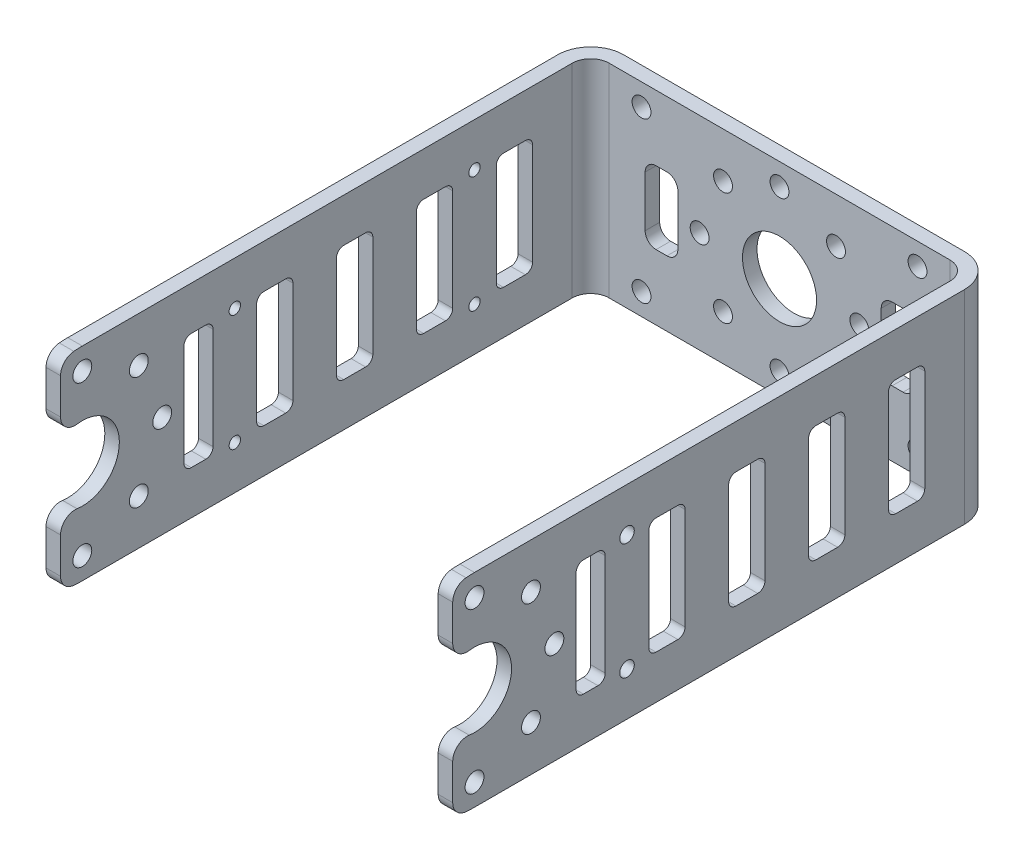
SolidWorks part; units mm, degrees
material "1060 Alloy"
ref_plane "Front Plane" through (0, 0, 0) normal (0, 0, 1) x (1, 0, 0)
ref_plane "Top Plane" through (0, 0, 0) normal (0, 1, 0) x (1, 0, 0)
ref_plane "Right Plane" through (0, 0, 0) normal (1, 0, 0) x (0, 0, -1)
ref_plane "Plane1" through (-2, 0, 0) normal (-1, 0, 0) x (0, -1, 0)
sketch "Sketch1" plane through (-2, 0, 0) normal (-1, 0, 0) x (0, -1, 0)
  line L0 (-28, 72) -> (0, 72)
  line L1 (-0.3252, 75) -> (-27.6748, 75)
  arc A0 (-27.6748, 75) -> (-28, 72) centre (-14, 72) ccw
  arc A1 (0, 72) -> (-0.3252, 75) centre (-14, 72) ccw
extrude "Boss-Extrude1" add sketch "Sketch1" against normal blind 54
sketch "Sketch2" plane through (0, 0, 72) normal (0, 0, -1) x (-1, 0, 0)
  line L0 (-52, 28) -> (2, 28)
  line L1 (2, 28) -> (2, 0)
  line L2 (2, 0) -> (-52, 0)
  line L3 (-52, 0) -> (-52, 28)
extrude "Boss-Extrude2" add sketch "Sketch2" along normal blind 72
sketch "Sketch3" plane through (52, 0, 0) normal (1, 0, 0) x (0, 0, -1)
  line L0 (-72, 0) -> (-72, 28)
  line L1 (-75, 27.6748) -> (-75, 0.3252)
  arc A0 (-72, 28) -> (-75, 27.6748) centre (-72, 14) ccw
  arc A1 (-75, 0.3252) -> (-72, 0) centre (-72, 14) ccw
extrude "Cut-Extrude1" cut sketch "Sketch3" against normal blind 52
sketch "Sketch4" plane through (0, 0, 72) normal (0, 0, 1) x (1, 0, 0)
  line L0 (52, 28) -> (0, 28)
  line L1 (0, 28) -> (0, 0)
  line L2 (0, 0) -> (52, 0)
  line L3 (52, 0) -> (52, 28)
extrude "Cut-Extrude2" cut sketch "Sketch4" against normal blind 70
sketch "Sketch5" plane through (52, 0, 0) normal (1, 0, 0) x (0, 0, -1)
  line L0 (-72, 28) -> (0, 28)
  line L1 (0, 28) -> (0, 0)
  line L2 (0, 0) -> (-72, 0)
  line L3 (-75, 0.3252) -> (-75, 27.6748)
  arc A0 (-75, 27.6748) -> (-72, 28) centre (-72, 14) cw
  arc A1 (-72, 0) -> (-75, 0.3252) centre (-72, 14) cw
extrude "Boss-Extrude3" add sketch "Sketch5" along normal blind 2
sketch "Sketch6" plane through (52, 0, 0) normal (-1, 0, 0) x (0, 0, 1)
  line L0 (21, 22) -> (21, 6)
  line L1 (21, 6) -> (26, 6)
  line L2 (26, 6) -> (26, 22)
  line L3 (26, 22) -> (21, 22)
extrude "Cut-Extrude3" cut sketch "Sketch6" against normal through all
sketch "Sketch7" plane through (52, 0, 0) normal (-1, 0, 0) x (0, 0, 1)
  line L0 (10, 22) -> (10, 6)
  line L1 (10, 6) -> (15, 6)
  line L2 (15, 6) -> (15, 22)
  line L3 (15, 22) -> (10, 22)
extrude "Cut-Extrude4" cut sketch "Sketch7" against normal through all
sketch "Sketch8" plane through (52, 0, 0) normal (-1, 0, 0) x (0, 0, 1)
  line L0 (48, 6) -> (48, 22)
  line L1 (48, 22) -> (43, 22)
  line L2 (43, 22) -> (43, 6)
  line L3 (43, 6) -> (48, 6)
extrude "Cut-Extrude5" cut sketch "Sketch8" against normal through all
sketch "Sketch9" plane through (52, 0, 0) normal (-1, 0, 0) x (0, 0, 1)
  line L0 (58, 6) -> (58, 22)
  line L1 (58, 22) -> (54, 22)
  line L2 (54, 22) -> (54, 6)
  line L3 (54, 6) -> (58, 6)
extrude "Cut-Extrude6" cut sketch "Sketch9" against normal through all
sketch "Sketch10" plane through (0, 0, 2) normal (0, 0, 1) x (1, 0, 0)
  line L0 (7.5, 9) -> (12, 9)
  line L1 (12, 9) -> (12, 19)
  line L2 (12, 19) -> (7.5, 19)
  line L3 (7.5, 19) -> (7.5, 9)
extrude "Cut-Extrude7" cut sketch "Sketch10" against normal through all
sketch "Sketch11" plane through (0, 0, 0) normal (1, 0, 0) x (0, 0, -1)
  line L0 (-58, 6) -> (-54, 6)
  line L1 (-54, 6) -> (-54, 22)
  line L2 (-54, 22) -> (-58, 22)
  line L3 (-58, 22) -> (-58, 6)
extrude "Cut-Extrude8" cut sketch "Sketch11" against normal through all
sketch "Sketch12" plane through (0, 0, 0) normal (1, 0, 0) x (0, 0, -1)
  line L0 (-48, 22) -> (-48, 6)
  line L1 (-48, 6) -> (-43, 6)
  line L2 (-43, 6) -> (-43, 22)
  line L3 (-43, 22) -> (-48, 22)
extrude "Cut-Extrude9" cut sketch "Sketch12" against normal through all
sketch "Sketch13" plane through (0, 0, 0) normal (1, 0, 0) x (0, 0, -1)
  line L0 (-10, 6) -> (-10, 22)
  line L1 (-10, 22) -> (-15, 22)
  line L2 (-15, 22) -> (-15, 6)
  line L3 (-15, 6) -> (-10, 6)
extrude "Cut-Extrude10" cut sketch "Sketch13" against normal through all
sketch "Sketch14" plane through (0, 0, 0) normal (1, 0, 0) x (0, 0, -1)
  line L0 (-21, 6) -> (-21, 22)
  line L1 (-21, 22) -> (-26, 22)
  line L2 (-26, 22) -> (-26, 6)
  line L3 (-26, 6) -> (-21, 6)
extrude "Cut-Extrude11" cut sketch "Sketch14" against normal through all
sketch "Sketch15" plane through (0, 0, 0) normal (1, 0, 0) x (0, 0, -1)
  line L0 (-32, 6) -> (-32, 22)
  line L1 (-32, 22) -> (-37, 22)
  line L2 (-37, 22) -> (-37, 6)
  line L3 (-37, 6) -> (-32, 6)
extrude "Cut-Extrude12" cut sketch "Sketch15" against normal through all
sketch "Sketch16" plane through (0, 0, 2) normal (0, 0, 1) x (1, 0, 0)
  line L0 (44.5, 9) -> (44.5, 19)
  line L1 (44.5, 19) -> (40, 19)
  line L2 (40, 19) -> (40, 9)
  line L3 (40, 9) -> (44.5, 9)
extrude "Cut-Extrude13" cut sketch "Sketch16" against normal through all
sketch "Sketch17" plane through (54, 0, 0) normal (1, 0, 0) x (0, 0, -1)
  line L0 (-37, 6) -> (-32, 6)
  line L1 (-32, 6) -> (-32, 22)
  line L2 (-32, 22) -> (-37, 22)
  line L3 (-37, 22) -> (-37, 6)
extrude "Cut-Extrude14" cut sketch "Sketch17" against normal through all
hole_wizard "Ø2.0 (2) Diameter Hole1" positions "Sketch19" profile "Sketch18" hole size "Ø2.0" standard "ANSI Metric"
sketch "Sketch19" plane through (52, 0, 0) normal (-1, 0, 0) x (0, 0, 1)
  point P0 (51, 22)
  point P1 (51, 6)
sketch "Sketch18" plane through (52, 22, 51) normal (0, 1, 0) x (0, 0, 1)
  line L0 (0, 0) -> (0, 2)
  line L1 (0, 2) -> (1, 2)
  line L2 (1, 2) -> (1, 0)
  line L5 (1, 0) -> (0, 0)
  line L11 (0, -6.35) -> (0, 107.95) construction
  dimension "Thru Hole Dia." = 2
  dimension "Thru Hole Depth" = 2
hole_wizard "Ø2.6 (2.6) Diameter Hole1" positions "Sketch21" profile "Sketch20" hole size "Ø2.6" standard "ANSI Metric"
sketch "Sketch21" plane through (52, 0, 0) normal (-1, 0, 0) x (0, 0, 1)
  point P0 (72, 25)
  point P1 (72, 3)
  point P2 (64.2218, 21.7782)
  point P3 (64.2218, 6.2218)
  point P4 (61, 14)
sketch "Sketch20" plane through (52, 25, 72) normal (0, 1, 0) x (0, 0, 1)
  line L0 (0, 0) -> (0, 2)
  line L1 (0, 2) -> (1.3, 2)
  line L2 (1.3, 2) -> (1.3, 0)
  line L5 (1.3, 0) -> (0, 0)
  line L11 (0, -6.35) -> (0, 107.95) construction
  dimension "Thru Hole Dia." = 2.6
  dimension "Thru Hole Depth" = 2
hole_wizard "Ø10.2 (10.2) Diameter Hole1" positions "Sketch23" profile "Sketch22" hole size "Ø10.2" standard "ANSI Metric"
sketch "Sketch23" plane through (54, 0, 0) normal (1, 0, 0) x (0, 0, -1)
  point P0 (-72, 14)
sketch "Sketch22" plane through (54, 14, 72) normal (0, 1, 0) x (0, 0, -1)
  line L0 (0, 0) -> (0, 2)
  line L1 (0, 2) -> (5.1, 2)
  line L2 (5.1, 2) -> (5.1, 0)
  line L5 (5.1, 0) -> (0, 0)
  line L11 (0, -6.35) -> (0, 107.95) construction
  dimension "Thru Hole Dia." = 10.2
  dimension "Thru Hole Depth" = 2
hole_wizard "Ø2.6 (2.6) Diameter Hole2" positions "Sketch25" profile "Sketch24" hole size "Ø2.6" standard "ANSI Metric"
sketch "Sketch25" plane through (0, 0, 0) normal (1, 0, 0) x (0, 0, -1)
  point P0 (-72, 25)
  point P1 (-72, 3)
  point P2 (-64.2218, 21.7782)
  point P3 (-64.2218, 6.2218)
  point P4 (-61, 14)
sketch "Sketch24" plane through (0, 25, 72) normal (0, 1, 0) x (0, 0, -1)
  line L0 (0, 0) -> (0, 2)
  line L1 (0, 2) -> (1.3, 2)
  line L2 (1.3, 2) -> (1.3, 0)
  line L5 (1.3, 0) -> (0, 0)
  line L11 (0, -6.35) -> (0, 107.95) construction
  dimension "Thru Hole Dia." = 2.6
  dimension "Thru Hole Depth" = 2
hole_wizard "Hole1" positions "Sketch27" profile "Sketch26" legacy
sketch "Sketch27" plane through (0, 0, 0) normal (1, 0, 0) x (0, 0, -1)
  point P0 (-18, 22)
  point P1 (-18, 6)
  point P2 (-51, 6)
  point P3 (-51, 22)
sketch "Sketch26" plane through (0, 22, 18) normal (0, 1, 0) x (0, 0, -1)
  line L0 (0, 0) -> (0, 2)
  line L1 (0, 2) -> (0.7835, 2)
  line L2 (0.7835, 2) -> (0.7835, 0)
  line L3 (0.7835, 0) -> (0, 0)
  line L4 (0, 110) -> (0, -10) construction
  dimension "Diameter" = 1.567
  dimension "Depth" = 2
hole_wizard "Ø10.2 (10.2) Diameter Hole2" positions "Sketch29" profile "Sketch28" hole size "Ø10.2" standard "ANSI Metric"
sketch "Sketch29" plane through (0, 0, 0) normal (1, 0, 0) x (0, 0, -1)
  point P0 (-72, 14)
sketch "Sketch28" plane through (0, 14, 72) normal (0, 1, 0) x (0, 0, -1)
  line L0 (0, 0) -> (0, 2)
  line L1 (0, 2) -> (5.1, 2)
  line L2 (5.1, 2) -> (5.1, 0)
  line L5 (5.1, 0) -> (0, 0)
  line L11 (0, -6.35) -> (0, 107.95) construction
  dimension "Thru Hole Dia." = 10.2
  dimension "Thru Hole Depth" = 2
hole_wizard "Ø10.2 (10.2) Diameter Hole3" positions "Sketch31" profile "Sketch30" hole size "Ø10.2" standard "ANSI Metric"
sketch "Sketch31" plane through (0, 0, 2) normal (0, 0, 1) x (1, 0, 0)
  point P0 (26, 14)
sketch "Sketch30" plane through (26, 14, 2) normal (1, 0, 0) x (0, -1, 0)
  line L0 (0, 0) -> (0, 2)
  line L1 (0, 2) -> (5.1, 2)
  line L2 (5.1, 2) -> (5.1, 0)
  line L5 (5.1, 0) -> (0, 0)
  line L11 (0, -6.35) -> (0, 107.95) construction
  dimension "Thru Hole Dia." = 10.2
  dimension "Thru Hole Depth" = 2
hole_wizard "Ø2.6 (2.6) Diameter Hole3" positions "Sketch33" profile "Sketch32" hole size "Ø2.6" standard "ANSI Metric"
sketch "Sketch33" plane through (0, 0, 2) normal (0, 0, 1) x (1, 0, 0)
  point P0 (45, 3)
  point P1 (7, 3)
  point P2 (45, 25)
  point P3 (7, 25)
  point P4 (26, 25)
  point P5 (18.2218, 21.7782)
  point P6 (15, 14)
  point P7 (18.2218, 6.2218)
  point P8 (26, 3)
  point P9 (33.7782, 6.2218)
  point P10 (37, 14)
  point P11 (33.7782, 21.7782)
sketch "Sketch32" plane through (45, 3, 2) normal (1, 0, 0) x (0, -1, 0)
  line L0 (0, 0) -> (0, 2)
  line L1 (0, 2) -> (1.3, 2)
  line L2 (1.3, 2) -> (1.3, 0)
  line L5 (1.3, 0) -> (0, 0)
  line L11 (0, -6.35) -> (0, 107.95) construction
  dimension "Thru Hole Dia." = 2.6
  dimension "Thru Hole Depth" = 2
fillet "Fillet1" radius 1 40 edges at (-1, 22, 48) (53, 22, 58) (53, 22, 48) (-1, 22, 58) (-1, 6, 10) (-1, 6, 58) (53, 6, 15) (53, 22, 32) (53, 22, 43) (53, 6, 37) (53, 22, 54) (53, 6, 21) (-1, 6, 48) (53, 6, 26) (-1, 22, 54) (53, 6, 10) (53, 22, 37) (-1, 22, 32) (53, 22, 21) (-1, 6, 37) (53, 22, 26) (-1, 6, 32) (53, 22, 10) (-1, 22, 37) (53, 22, 15) (-1, 22, 26) (53, 6, 48) (-1, 22, 21) (53, 6, 43) (-1, 6, 26) (53, 6, 58) (-1, 6, 21) (53, 6, 54) (-1, 22, 15) (-1, 6, 43) (-1, 22, 10) (-1, 22, 43) (-1, 6, 15) (-1, 6, 54) (53, 6, 32) tangent propagation no
fillet "Fillet2" radius 1.5 8 edges at (7.5, 9, 1) (12, 19, 1) (40, 9, 1) (40, 19, 1) (12, 9, 1) (44.5, 19, 1) (44.5, 9, 1) (7.5, 19, 1) tangent propagation no
fillet "Fillet3" radius 2 8 edges at (53, 27.6748, 75) (53, 0.3252, 75) (-1, 9.8757, 75) (53, 9.8757, 75) (53, 18.1243, 75) (-1, 0.3252, 75) (-1, 18.1243, 75) (-1, 27.6748, 75) tangent propagation no
fillet "Fillet4" radius 2.54 2 edges at (52, 14, 2) (0, 14, 2) tangent propagation no
fillet "Fillet5" radius 4.54 2 edges at (54, 14, 0) (-2, 14, 0) tangent propagation no
ref_axis "Axis1" through (26, 14, 0) along (0, 0, 1)
